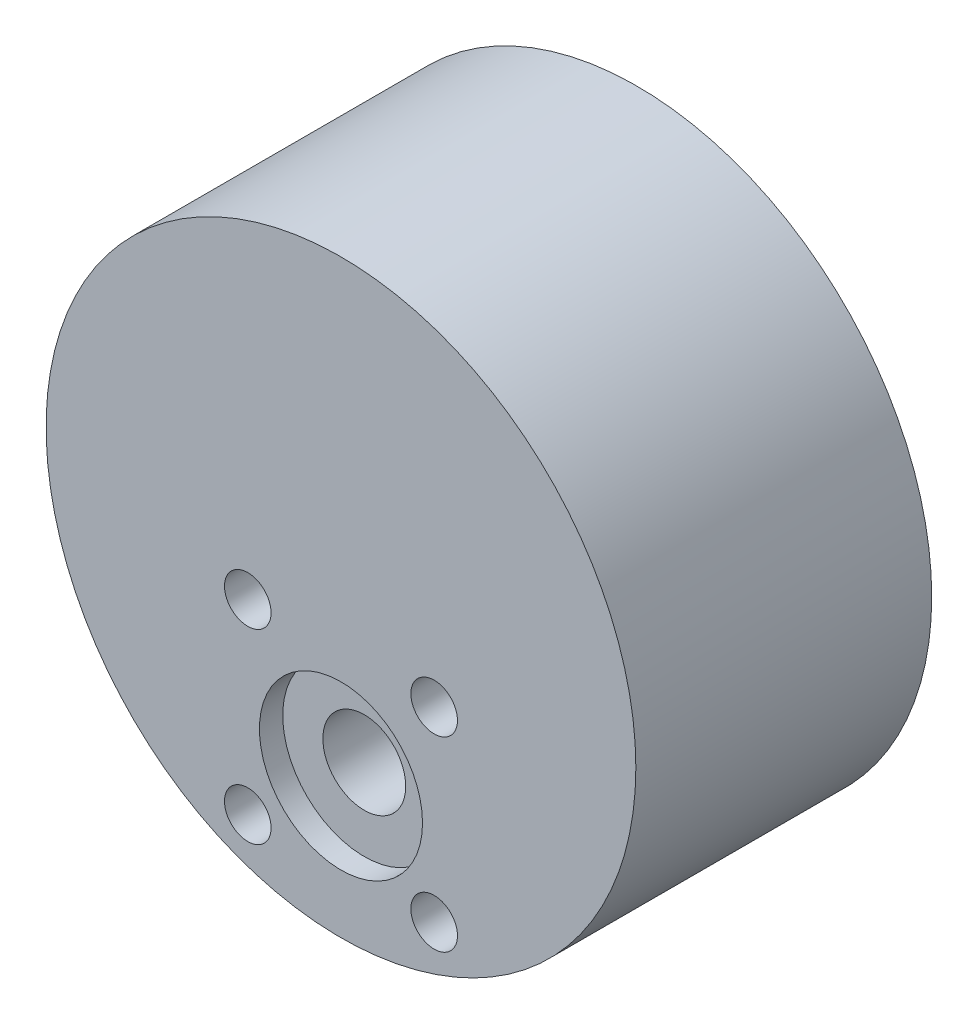
SolidWorks part; units mm, degrees
ref_plane "Front Plane" through (0, 0, 0) normal (0, 0, 1) x (1, 0, 0)
ref_plane "Top Plane" through (0, 0, 0) normal (0, 1, 0) x (1, 0, 0)
ref_plane "Right Plane" through (0, 0, 0) normal (1, 0, 0) x (0, 0, -1)
sketch "Sketch1" plane through (0, 0, 0) normal (0, 0, 1) x (1, 0, 0)
  circle A0 centre (0, 0) radius 25.3146
extrude "Boss-Extrude1" add sketch "Sketch1" along normal blind 25.4
sketch "Sketch2" plane through (0, 0, 25.4) normal (0, 0, 1) x (1, 0, 0)
  circle A0 centre (0, -13.2788) radius 3.556
  dimension "D1" = 7.112
extrude "Cut-Extrude1" cut sketch "Sketch2" against normal blind 25.4
sketch "Sketch3" plane through (0, 0, 25.4) normal (0, 0, 1) x (1, 0, 0)
  circle A0 centre (0, -13.2788) radius 7
  circle A1 centre (0, 0) radius 25.3146
  circle A2 centre (0, 0) radius 25.3146
  circle A3 centre (0, -13.2788) radius 3.175
  circle M3 centre (0, -13.2788) radius 3.556
  dimension "D2" = 14
  dimension "D1" = 0
extrude "Cut-Extrude2" cut sketch "Sketch3" against normal blind 2 contours A0 M3 region at (-6.802, -13.2788, 25.4)
sketch "Sketch4" plane through (0, 0, 25.4) normal (0, 0, 1) x (1, 0, 0)
  circle A0 centre (-8, -4.1582) radius 2
  circle A1 centre (0, 0) radius 25.3146
  circle A2 centre (0, 0) radius 25.3146
  circle A3 centre (8, -4.1582) radius 2
  circle A4 centre (8, -20.1582) radius 2
  circle A5 centre (-8, -20.1582) radius 2
  circle A7 centre (0, -13.2788) radius 3.556 construction
  dimension "D2" = 16
  dimension "D3" = 16
  dimension "D4" = 16
  dimension "D5" = 16
  dimension "D6" = 16
  dimension "D7" = 8
  dimension "D8" = 4
  dimension "D9" = 4
  dimension "D10" = 4
  dimension "D1" = 0
extrude "Cut-Extrude3" cut sketch "Sketch4" against normal through all contours A5 | A4 | A3 | A0
